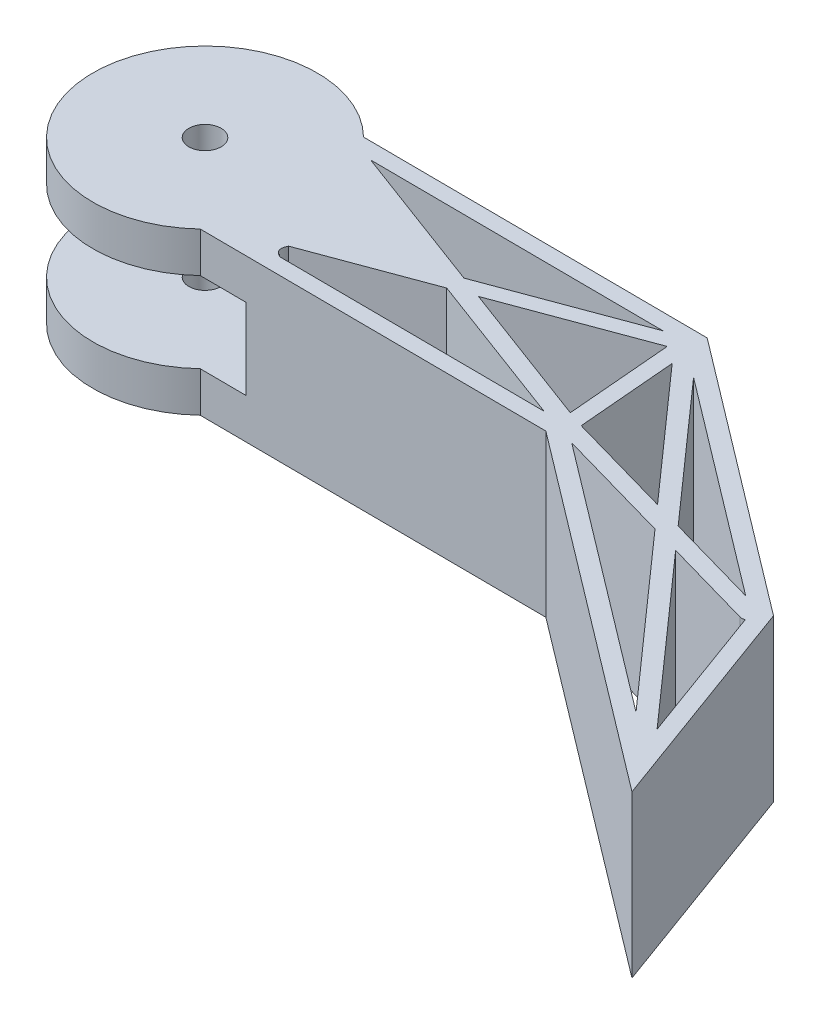
SolidWorks part; units mm, degrees
ref_plane "Front Plane" through (0, 0, 0) normal (0, 0, 1) x (1, 0, 0)
ref_plane "Top Plane" through (0, 0, 0) normal (0, 1, 0) x (1, 0, 0)
ref_plane "Right Plane" through (0, 0, 0) normal (1, 0, 0) x (0, 0, -1)
sketch "Sketch2" plane through (0, 0, 0) normal (0, 1, 0) x (1, 0, 0)
  line L0 (-86.903, -5.6011) -> (-1.9458, -5.6011) construction
  line L1 (-2.39, -19.0095) -> (53.5769, -61.4158)
  line L2 (53.5769, -61.4158) -> (40.7254, -26.2781)
  line L3 (-56.8329, 6.7281) -> (-2.3899, 6.3905)
  line L4 (40.7254, -26.2781) -> (-2.3899, 6.3905)
  line L6 (-57.1469, -18.67) -> (-2.39, -19.0095)
  arc A0 (-57.1469, -18.67) -> (-56.8329, 6.7281) centre (-69.2509, -5.8194) cw
  circle A1 centre (-69.2509, -5.8194) radius 2.54
  dimension "D3" = 25.4
extrude "Boss-Extrude4" add sketch "Sketch2" along normal blind 12.7
sketch "Sketch4" plane through (0, 12.7, 0) normal (0, 1, 0) x (1, 0, 0)
  circle A0 centre (-69.2509, -5.8194) radius 17.6534
extrude "Cut-Extrude1" cut sketch "Sketch4" against normal blind 6.35
sketch "Triangleout" plane through (0, 6.35, 0) normal (0, 1, 0) x (1, 0, 0)
  line L0 (-58.1063, -19.5103) -> (-49.4554, -19.5103)
  line L1 (-49.4554, -19.5103) -> (-53.0939, -12.9324)
  line L2 (-53.0939, -12.9324) -> (-58.1063, -19.5103)
  arc A0 (-57.1469, -18.67) -> (-56.8329, 6.7281) centre (-69.2509, -5.8194) ccw construction
  arc A1 (-56.8329, 6.7281) -> (-57.1469, -18.67) centre (-69.2509, -5.8194) ccw construction
extrude "Cut-Extrude2" cut sketch "Triangleout" along normal blind 6.35
mirror "Mirror3" about plane through (-69.2509, 12.7, 5.8194) normal (0, -1, 0) of "Cut-Extrude2", "Cut-Extrude1", "Boss-Extrude4"
sketch "Sketch5" plane through (0, 25.4, 0) normal (0, 1, 0) x (1, 0, 0)
  line L0 (-1.5294, -16.4748) -> (-3.2505, 3.8558) construction
  line L1 (48.2231, -54.1724) -> (-3.2505, 3.8558)
  line L2 (47.1512, -43.847) -> (-2.39, -6.3095) construction
  line L3 (-57.1312, -16.1301) -> (-3.2505, 3.8558)
  line L4 (53.5769, -61.4158) -> (40.7254, -26.2781) construction
  line L5 (-56.9899, -5.971) -> (-2.39, -6.3095) construction
  line L6 (-57.1469, -18.67) -> (-56.8329, 6.7281) construction
  line L7 (-56.8486, 4.1881) -> (-1.5294, -16.4748)
  line L8 (-1.5294, -16.4748) -> (38.5964, -27.8518)
  line L10 (-56.6895, -17.3208) -> (-3.6238, 2.3628)
  line L11 (47.273, -55.0152) -> (-3.6238, 2.3628)
  line L12 (-57.293, 2.9984) -> (-1.9254, -17.6825)
  line L13 (-1.9254, -17.6825) -> (38.25, -29.0736)
  line L14 (-57.5729, -14.9393) -> (-2.8772, 5.3488)
  line L15 (49.1732, -53.3296) -> (-2.8772, 5.3488)
  line L16 (-56.4043, 5.3778) -> (-1.1333, -15.267)
  line L17 (-1.1333, -15.267) -> (38.9428, -26.6299)
  line L18 (-1.5294, -16.4748) -> (-3.2505, 3.8558)
  line L19 (-0.2639, -16.3676) -> (-1.9851, 3.963)
  line L20 (-2.7949, -16.5819) -> (-4.516, 3.7487)
  line L28 (-3.2505, 3.8558) -> (-56.8486, 4.1881)
  line L29 (38.5964, -27.8518) -> (-3.2505, 3.8558)
  line L30 (48.2231, -54.1724) -> (38.5964, -27.8518)
  line L31 (-1.5294, -16.4748) -> (48.2231, -54.1724)
  line L32 (-57.1312, -16.1301) -> (-1.5294, -16.4748)
  line L33 (-3.2505, 3.8558) -> (-56.8486, 4.1881)
  line L34 (38.5964, -27.8518) -> (-3.2505, 3.8558)
  line L35 (48.2231, -54.1724) -> (38.5964, -27.8518)
  line L36 (-1.5294, -16.4748) -> (48.2231, -54.1724)
  line L37 (-57.1312, -16.1301) -> (-1.5294, -16.4748)
  arc A0 (-56.6895, -17.3208) -> (-57.5729, -14.9393) centre (-57.1312, -16.1301) cw
  arc A1 (47.273, -55.0152) -> (49.1732, -53.3296) centre (48.2231, -54.1724) ccw
  arc A2 (-57.293, 2.9984) -> (-56.4043, 5.3778) centre (-56.8486, 4.1881) cw
  arc A3 (38.25, -29.0736) -> (38.9428, -26.6299) centre (38.5964, -27.8518) ccw
  arc A4 (-0.2639, -16.3676) -> (-2.7949, -16.5819) centre (-1.5294, -16.4748) cw
  arc A5 (-1.9851, 3.963) -> (-4.516, 3.7487) centre (-3.2505, 3.8558) ccw
  arc A7 (-57.1469, -18.67) -> (-56.8329, 6.7281) centre (-69.6889, -5.814) ccw
  spline S0 degree 1 poles (-57.1312, -16.1301) (-56.8486, 4.1881) knots 0 0 1 1
  spline S1 degree 2 poles (-47.0825, -16.1924) (-48.6344, -15.5095) (-47.8598, -14.0456) knots 0 0 0 1 1 1
  dimension "D1" = 2.54
  dimension "D2" = 1.27
  dimension "D3" = 1.27
  dimension "D4" = 1.27
  dimension "D5" = 1.27
extrude "Cut-Extrude5" cut sketch "Sketch5" against normal through all contours L10 L37 L12 | L14 L33 L16 | L16 L20 L10 | A3 L13 L15 L35 | L13 L36 L11 | L17 L34 L15 | L19 L17 L11 region at (36.756, 25.4, 35.0972) region at (21.2871, 25.4, 30.8694) region at (4.8107, 25.4, 11.8628) region at (19.5694, 25.4, 15.7811) region at (-28.9114, 25.4, 13.242) region at (-11.1317, 25.4, 6.1523) region at (-29.8984, 25.4, -1.1482)
